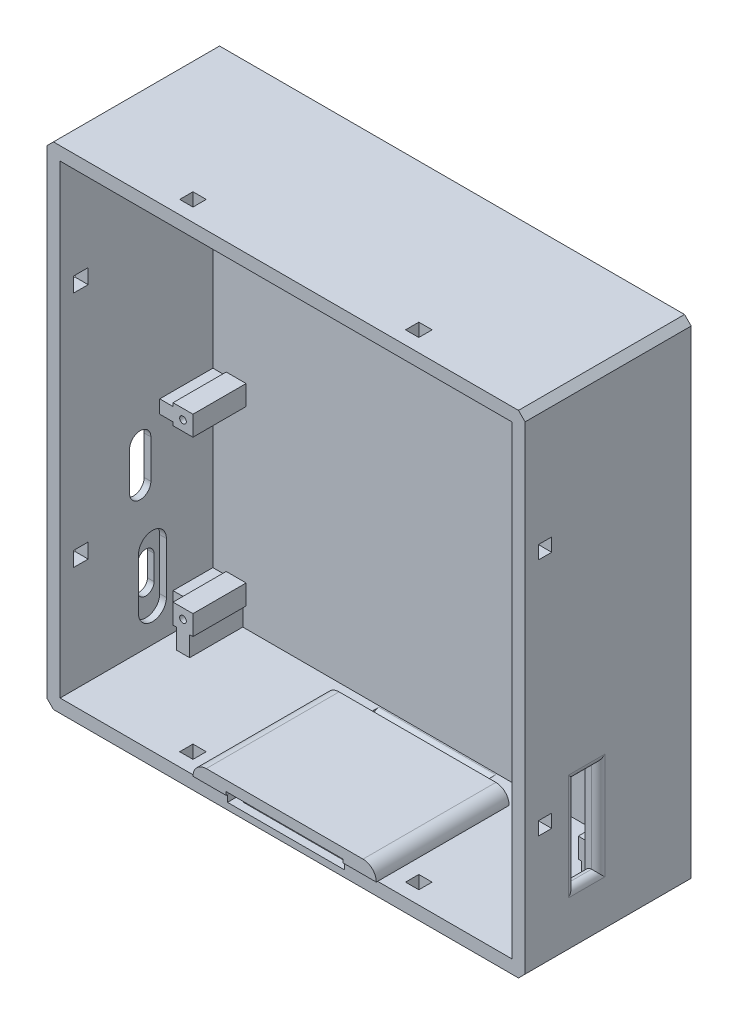
SolidWorks part; units mm, degrees
ref_plane "前视基准面" through (0, 0, 0) normal (0, 0, 1) x (1, 0, 0)
ref_plane "上视基准面" through (0, 0, 0) normal (0, 1, 0) x (1, 0, 0)
ref_plane "右视基准面" through (0, 0, 0) normal (1, 0, 0) x (0, 0, -1)
sketch "草图1" plane through (0, 0, 0) normal (0, 0, 1) x (1, 0, 0)
  line L1 (-21.8087, 48.178) -> (50.1913, 48.178)
  line L2 (-21.8087, 48.178) -> (-21.8087, -25.822)
  line L3 (-21.8087, -25.822) -> (50.1913, -25.822)
  line L4 (50.1913, 48.178) -> (50.1913, -25.822)
  dimension "D1" = 74
  dimension "D2" = 72
extrude "凸台-拉伸1" add sketch "草图1" along normal blind 25
sketch "草图2" plane through (0, 0, 25) normal (0, 0, 1) x (1, 0, 0)
  line L0 (50.1913, 48.178) -> (-21.8087, 48.178) construction
  line L1 (-19.8087, 46.178) -> (48.1913, 46.178)
  line L2 (-19.8087, 46.178) -> (-19.8087, -23.822)
  line L3 (-19.8087, -23.822) -> (48.1913, -23.822)
  line L4 (48.1913, 46.178) -> (48.1913, -23.822)
  line L5 (-21.8087, -25.822) -> (50.1913, -25.822) construction
  line L6 (50.1913, -25.822) -> (50.1913, 48.178) construction
  line L7 (-21.8087, 48.178) -> (-21.8087, -25.822) construction
  dimension "D1" = 2
  dimension "D2" = 2
  dimension "D3" = 2
  dimension "D4" = 2
extrude "切除-拉伸1" cut sketch "草图2" against normal blind 23
sketch "草图3" plane through (0, 46.178, 0) normal (0, -1, 0) x (1, 0, 0)
  line L0 (48.1913, 25) -> (-19.8087, 25) construction
  line L1 (-3.8087, 23) -> (-1.8087, 23)
  line L2 (-3.8087, 23) -> (-3.8087, 21)
  line L3 (-3.8087, 21) -> (-1.8087, 21)
  line L4 (-1.8087, 23) -> (-1.8087, 21)
  line L5 (30.1913, 23) -> (32.1913, 23)
  line L6 (30.1913, 23) -> (30.1913, 21)
  line L7 (30.1913, 21) -> (32.1913, 21)
  line L8 (32.1913, 23) -> (32.1913, 21)
  line L9 (48.1913, 2) -> (48.1913, 25) construction
  line L10 (-19.8087, 2) -> (-19.8087, 25) construction
  dimension "D1" = 2
  dimension "D2" = 2
  dimension "D3" = 2
  dimension "D4" = 16
  dimension "D5" = 16
extrude "切除-拉伸2" cut sketch "草图3" against normal up to next
sketch "草图4" plane through (48.1913, 0, 0) normal (-1, 0, 0) x (0, 0, 1)
  line L1 (23, 30.178) -> (21, 30.178)
  line L2 (23, 30.178) -> (23, 28.178)
  line L3 (23, 28.178) -> (21, 28.178)
  line L4 (21, 30.178) -> (21, 28.178)
  line L5 (23, -5.822) -> (21, -5.822)
  line L6 (23, -5.822) -> (23, -7.822)
  line L7 (23, -7.822) -> (21, -7.822)
  line L8 (21, -5.822) -> (21, -7.822)
  line L10 (25, -23.822) -> (25, 46.178) construction
  line L11 (2, 46.178) -> (25, 46.178) construction
  line L12 (2, -23.822) -> (25, -23.822) construction
  dimension "D1" = 2
  dimension "D2" = 2
  dimension "D3" = 2
  dimension "D4" = 16
  dimension "D5" = 16
sketch "草图5" plane through (0, -23.822, 0) normal (0, 1, 0) x (1, 0, 0)
  line L0 (-19.8087, -25) -> (48.1913, -25) construction
  line L1 (32.1913, -23) -> (30.1913, -23)
  line L2 (32.1913, -23) -> (32.1913, -21)
  line L3 (32.1913, -21) -> (30.1913, -21)
  line L4 (30.1913, -23) -> (30.1913, -21)
  line L5 (-1.8087, -23) -> (-3.8087, -23)
  line L6 (-1.8087, -23) -> (-1.8087, -21)
  line L7 (-1.8087, -21) -> (-3.8087, -21)
  line L8 (-3.8087, -23) -> (-3.8087, -21)
  line L9 (48.1913, -2) -> (48.1913, -25) construction
  line L10 (-19.8087, -2) -> (-19.8087, -25) construction
  dimension "D1" = 2
  dimension "D2" = 2
  dimension "D3" = 16
  dimension "D4" = 16
sketch "草图6" plane through (-19.8087, 0, 0) normal (1, 0, 0) x (0, 0, -1)
  line L0 (-25, 46.178) -> (-25, -23.822) construction
  line L1 (-23, 30.178) -> (-20.7747, 30.178)
  line L2 (-23, 30.178) -> (-23, 27.9527)
  line L3 (-23, 27.9527) -> (-20.7747, 27.9527)
  line L4 (-20.7747, 30.178) -> (-20.7747, 27.9527)
  line L5 (-23, -5.5967) -> (-20.7747, -5.5967)
  line L6 (-23, -5.5967) -> (-23, -7.822)
  line L7 (-23, -7.822) -> (-20.7747, -7.822)
  line L8 (-20.7747, -5.5967) -> (-20.7747, -7.822)
  line L9 (-2, -23.822) -> (-25, -23.822) construction
  line L10 (-2, 46.178) -> (-25, 46.178) construction
  dimension "D1" = 2
  dimension "D2" = 16
  dimension "D3" = 16
extrude "切除-拉伸3" cut sketch "草图4" against normal up to next
extrude "切除-拉伸4" cut sketch "草图5" against normal up to next
extrude "切除-拉伸5" cut sketch "草图6" against normal up to next
sketch "草图7" plane through (0, 0, 2) normal (0, 0, 1) x (1, 0, 0)
  line L1 (-17.8087, -20.822) -> (-14.8087, -20.822)
  line L2 (-17.8087, -20.822) -> (-17.8087, -17.822)
  line L3 (-17.8087, -17.822) -> (-14.8087, -17.822)
  line L4 (-14.8087, -20.822) -> (-14.8087, -17.822)
  line L5 (-17.8087, 5.178) -> (-14.8087, 5.178)
  line L6 (-17.8087, 5.178) -> (-17.8087, 8.178)
  line L7 (-17.8087, 8.178) -> (-14.8087, 8.178)
  line L8 (-14.8087, 5.178) -> (-14.8087, 8.178)
  line L9 (43.1913, -20.822) -> (46.1913, -20.822)
  line L10 (43.1913, -20.822) -> (43.1913, -17.822)
  line L11 (43.1913, -17.822) -> (46.1913, -17.822)
  line L12 (46.1913, -20.822) -> (46.1913, -17.822)
  line L13 (43.1913, 5.178) -> (46.1913, 5.178)
  line L14 (43.1913, 5.178) -> (43.1913, 8.178)
  line L15 (43.1913, 8.178) -> (46.1913, 8.178)
  line L16 (46.1913, 5.178) -> (46.1913, 8.178)
  line L18 (48.1913, -23.822) -> (48.1913, 46.178) construction
  line L19 (-19.8087, 46.178) -> (-19.8087, -23.822) construction
  line L20 (-19.8087, -23.822) -> (48.1913, -23.822) construction
  dimension "D1" = 3
  dimension "D2" = 23
  dimension "D3" = 2
  dimension "D4" = 3
  dimension "D5" = 2
extrude "凸台-拉伸2" add sketch "草图7" along normal blind 8
sketch "草图10" plane through (0, 0, 10) normal (0, 0, 1) x (1, 0, 0)
  line L0 (-17.8087, -17.822) -> (-14.8087, -20.822) construction
  line L1 (-14.8087, -20.822) -> (-14.8087, -17.822) construction
  line L2 (-14.8087, -17.822) -> (-17.8087, -20.822) construction
  line L3 (43.1913, 8.178) -> (46.1913, 5.178) construction
  line L4 (46.1913, 5.178) -> (46.1913, 8.178) construction
  line L5 (46.1913, 8.178) -> (43.1913, 5.178) construction
  circle A0 centre (44.6913, 6.678) radius 0.5
  circle A1 centre (44.6913, -19.322) radius 0.5
  circle A2 centre (-16.3087, -19.322) radius 0.5
  circle A3 centre (-16.3087, 6.678) radius 0.5
  point P17 (-16.3087, -19.322)
  point P26 (44.6913, 6.678)
  dimension "D1" = 1
extrude "切除-拉伸6" cut sketch "草图10" against normal blind 6
sketch "草图12" plane through (-17.8087, 0, 0) normal (-1, 0, 0) x (0, 0, 1)
  line L1 (2, -18.322) -> (8, -18.322)
  line L2 (2, -18.322) -> (2, -20.322)
  line L3 (2, -20.322) -> (8, -20.322)
  line L4 (8, -18.322) -> (8, -20.322)
  line L5 (2, -17.822) -> (2, -20.822) construction
  line L6 (10, -17.822) -> (10, -20.822) construction
  line L7 (2, 7.678) -> (10, 7.678)
  line L8 (2, 7.678) -> (2, 5.678)
  line L9 (2, 5.678) -> (10, 5.678)
  line L10 (10, 7.678) -> (10, 5.678)
  line L11 (10, 5.178) -> (2, 5.178) construction
  line L12 (10, 8.178) -> (10, 5.178) construction
  line L13 (2, 8.178) -> (2, 5.178) construction
  line L14 (10, -20.822) -> (2, -20.822) construction
  dimension "D1" = 0.5
  dimension "D2" = 2
  dimension "D3" = 2
  dimension "D4" = 0.5
  dimension "D5" = 2
extrude "凸台-拉伸3" add sketch "草图12" along normal up to next
sketch "草图13" plane through (46.1913, 0, 0) normal (1, 0, 0) x (0, 0, -1)
  line L1 (-10, 7.678) -> (-2, 7.678)
  line L2 (-10, 7.678) -> (-10, 5.678)
  line L3 (-10, 5.678) -> (-2, 5.678)
  line L4 (-2, 7.678) -> (-2, 5.678)
  line L5 (-10, 5.178) -> (-10, 8.178) construction
  line L6 (-2, 5.178) -> (-2, 8.178) construction
  line L7 (-10, 5.178) -> (-2, 5.178) construction
  line L8 (-10, -20.822) -> (-10, -17.822) construction
  line L9 (-10, -18.322) -> (-2, -18.322)
  line L10 (-10, -18.322) -> (-10, -20.322)
  line L11 (-10, -20.322) -> (-2, -20.322)
  line L12 (-2, -18.322) -> (-2, -20.322)
  line L13 (-2, -20.822) -> (-2, -17.822) construction
  line L14 (-10, -20.822) -> (-2, -20.822) construction
  point P20 (-6, -20.822)
  dimension "D1" = 2
  dimension "D2" = 0.5
  dimension "D3" = 2
  dimension "D4" = 0.5
extrude "凸台-拉伸4" add sketch "草图13" along normal up to next
sketch "草图14" plane through (0, -20.822, 0) normal (0, -1, 0) x (1, 0, 0)
  line L0 (-17.8087, 10) -> (-14.8087, 10) construction
  line L1 (-17.3087, 10) -> (-15.3087, 10)
  line L2 (-17.3087, 10) -> (-17.3087, 2)
  line L3 (-17.3087, 2) -> (-15.3087, 2)
  line L4 (-15.3087, 10) -> (-15.3087, 2)
  line L5 (43.6913, 10) -> (45.6913, 10)
  line L6 (43.6913, 10) -> (43.6913, 4.0576)
  line L7 (43.6913, 4.0576) -> (45.6913, 4.0576)
  line L8 (45.6913, 10) -> (45.6913, 4.0576)
  line L9 (-17.8087, 2) -> (-14.8087, 2) construction
  line L11 (-17.8087, 10) -> (-17.8087, 2) construction
  line L13 (43.1913, 10) -> (43.1913, 2) construction
  dimension "D1" = 2
  dimension "D2" = 2
  dimension "D3" = 0.5
  dimension "D4" = 0.5
extrude "凸台-拉伸5" add sketch "草图14" along normal up to next
sketch "草图15" plane through (-21.8087, 0, 0) normal (-1, 0, 0) x (0, 0, 1)
  line L0 (12.94, 3.798) -> (12.94, -2.402) construction
  line L1 (16.54, 3.798) -> (16.54, -2.402)
  line L2 (9.34, 3.798) -> (9.34, -2.402)
  line L4 (25, -25.822) -> (0, -25.822) construction
  line L5 (0, 48.178) -> (0, -25.822) construction
  arc A0 (16.54, 3.798) -> (9.34, 3.798) centre (12.94, 3.798) ccw
  arc A1 (9.34, -2.402) -> (16.54, -2.402) centre (12.94, -2.402) ccw
  point P0 (12.94, -6.002)
  point P3 (12.94, 0.698)
  point P8 (9.34, 0.698)
  dimension "D3" = 19.82
  dimension "D1" = 6.2
  dimension "D2" = 7.2
  dimension "D4" = 9.34
extrude "切除-拉伸8" cut sketch "草图15" against normal blind 1
sketch "草图18" plane through (-20.8087, 0, 0) normal (-1, 0, 0) x (0, 0, 1)
  line L0 (12.94, 3.398) -> (12.94, -2.402) construction
  line L3 (14.54, 3.398) -> (14.54, -2.402)
  line L4 (11.34, 3.398) -> (11.34, -2.402)
  line L5 (16.54, -2.402) -> (16.54, 3.798) construction
  arc A2 (9.34, -2.402) -> (16.54, -2.402) centre (12.94, -2.402) ccw construction
  arc A3 (14.54, 3.398) -> (11.34, 3.398) centre (12.94, 3.398) ccw
  arc A4 (11.34, -2.402) -> (14.54, -2.402) centre (12.94, -2.402) ccw
  point P2 (12.94, 0.498)
  point P7 (12.94, 4.998)
  point P8 (12.94, -4.002)
  point P12 (12.94, -6.002)
  dimension "D1" = 3.2
  dimension "D2" = 9
  dimension "D3" = 2
  dimension "D4" = 2
extrude "切除-拉伸9" cut sketch "草图18" against normal blind 1
sketch "草图19" plane through (-19.8087, 0, 0) normal (1, 0, 0) x (0, 0, -1)
  line L0 (-11.1, -11.022) -> (-11.1, -18.722) construction
  line L1 (-9, -11.022) -> (-9, -18.722)
  line L2 (-13.2, -11.022) -> (-13.2, -18.722)
  line L3 (-2, 5.678) -> (-2, -18.322) construction
  line L4 (-2, -23.822) -> (-25, -23.822) construction
  arc A0 (-9, -11.022) -> (-13.2, -11.022) centre (-11.1, -11.022) ccw
  arc A1 (-13.2, -18.722) -> (-9, -18.722) centre (-11.1, -18.722) ccw
  point P2 (-11.1, -14.872)
  point P9 (-11.1, -20.822)
  dimension "D1" = 7.7
  dimension "D2" = 4.2
  dimension "D3" = 7
  dimension "D4" = 3
extrude "切除-拉伸10" cut sketch "草图19" against normal blind 1 contours L1 A1 L2 A0
sketch "草图20" plane through (-20.8087, 0, 0) normal (1, 0, 0) x (0, 0, -1)
  line L0 (-12.35, -16.722) -> (-12.35, -13.2168)
  line L1 (-9.85, -13.0402) -> (-9.85, -16.722)
  line L3 (-9, -11.022) -> (-9, -18.722) construction
  arc A0 (-9.85, -13.0402) -> (-12.35, -13.2168) centre (-11.1005, -13.122) ccw
  arc A1 (-12.35, -16.722) -> (-9.85, -16.722) centre (-11.1, -16.722) ccw
  arc A3 (-13.2, -18.722) -> (-9, -18.722) centre (-11.1, -18.722) ccw construction
  dimension "D4" = 0.85
  dimension "D5" = 1.25
  dimension "D6" = 1.2531
  dimension "D1" = 2.5
  dimension "D2" = 3.6
  dimension "D3" = 2
extrude "切除-拉伸11" cut sketch "草图20" against normal blind 1
sketch "草图21" plane through (50.1913, 0, 0) normal (1, 0, 0) x (0, 0, -1)
  line L0 (0, -25.822) -> (0, 48.178) construction
  line L1 (-17.5, -17.142) -> (-14, -17.142)
  line L2 (-17.5, -17.142) -> (-17.5, -3.142)
  line L3 (-17.5, -3.142) -> (-14, -3.142)
  line L4 (-14, -17.142) -> (-14, -3.142)
  line L5 (-25, -25.822) -> (0, -25.822) construction
  dimension "D1" = 17.5
  dimension "D2" = 3.5
  dimension "D3" = 8.68
  dimension "D4" = 14
extrude "切除-拉伸12" cut sketch "草图21" against normal up to next
sketch "草图22" plane through (0, -23.822, 0) normal (0, 1, 0) x (1, 0, 0)
  line L0 (48.1913, -2) -> (48.1913, -25) construction
  line L1 (5.3913, -25) -> (22.9913, -25)
  line L2 (5.3913, -25) -> (5.3913, -3.2)
  line L3 (5.3913, -3.2) -> (22.9913, -3.2)
  line L4 (22.9913, -25) -> (22.9913, -3.2)
  line L6 (-19.8087, -25) -> (48.1913, -25) construction
  dimension "D1" = 42.8
  dimension "D2" = 17.6
  dimension "D3" = 21.8
extrude "切除-拉伸13" cut sketch "草图22" against normal blind 1 contours L2 L1 L4 L3
sketch "草图24" plane through (0, -24.822, 0) normal (0, 1, 0) x (1, 0, 0)
  line L0 (5.3913, -25) -> (5.3913, -3.2) construction
  line L1 (6.5913, -23.8) -> (21.7913, -23.8)
  line L2 (6.5913, -23.8) -> (6.5913, -8.6)
  line L3 (6.5913, -8.6) -> (21.7913, -8.6)
  line L4 (21.7913, -23.8) -> (21.7913, -8.6)
  line L6 (5.3913, -25) -> (22.9913, -25) construction
  dimension "D1" = 15.2
  dimension "D2" = 15.2
  dimension "D3" = 1.2
  dimension "D4" = 1.2
extrude "切除-拉伸14" cut sketch "草图24" against normal blind 1
sketch "草图27" plane through (0, -23.822, 0) normal (0, 1, 0) x (1, 0, 0)
  line L0 (5.3913, -25) -> (5.3913, -3.2) construction
  line L1 (0.3913, -25.2) -> (27.9913, -25.2)
  line L2 (0.3913, -25.2) -> (0.3913, -5.2)
  line L3 (0.3913, -5.2) -> (27.9913, -5.2)
  line L4 (27.9913, -25.2) -> (27.9913, -5.2)
  line L5 (22.9913, -25) -> (22.9913, -3.2) construction
  line L6 (5.3913, -3.2) -> (22.9913, -3.2) construction
  dimension "D1" = 5
  dimension "D2" = 5
  dimension "D3" = 20
  dimension "D4" = 2
extrude "凸台-拉伸6" add sketch "草图27" along normal blind 2 contours L2 L1 L4 L3
sketch "草图28" plane through (0, 0, 25.2) normal (0, 0, 1) x (1, 0, 0)
  line L0 (0.3913, -23.822) -> (27.9913, -23.822) construction
  line L1 (5.3889, -23.822) -> (22.9913, -23.822)
  line L2 (5.3889, -23.822) -> (5.3889, -23.322)
  line L3 (5.3889, -23.322) -> (22.9913, -23.322)
  line L4 (22.9913, -23.822) -> (22.9913, -23.322)
  line L5 (22.9913, -24.822) -> (22.9913, -23.822) construction
  dimension "D1" = 0.5
extrude "切除-拉伸16" cut sketch "草图28" against normal up to next contours L2 L1 L4 L3
fillet "圆角1" radius 1 1 edges at (14.1913, -23.822, 3.2)
fillet "圆角2" radius 2 2 edges at (0.3913, -21.822, 15.2) (27.9913, -21.822, 15.2)
chamfer "倒角1" distance 1 angle 45 4 edges at (50.1913, -25.822, 12.5) (50.1913, 48.178, 12.5) (-21.8087, -25.822, 12.5) (-21.8087, 48.178, 12.5)
fillet "圆角3" radius 1 2 edges at (48.1913, -17.142, 15.75) (48.1913, -3.142, 15.75)
fillet "圆角4" radius 1 4 edges at (50.1913, -10.142, 17.5) (50.1913, -10.142, 14) (50.1913, -17.142, 15.75) (50.1913, -3.142, 15.75)
chamfer "倒角3" distance 0.5 angle 45 4 edges at (6.5913, -25.822, 16.2) (14.1913, -25.822, 8.6) (21.7913, -25.822, 16.2) (14.1913, -25.822, 23.8)
